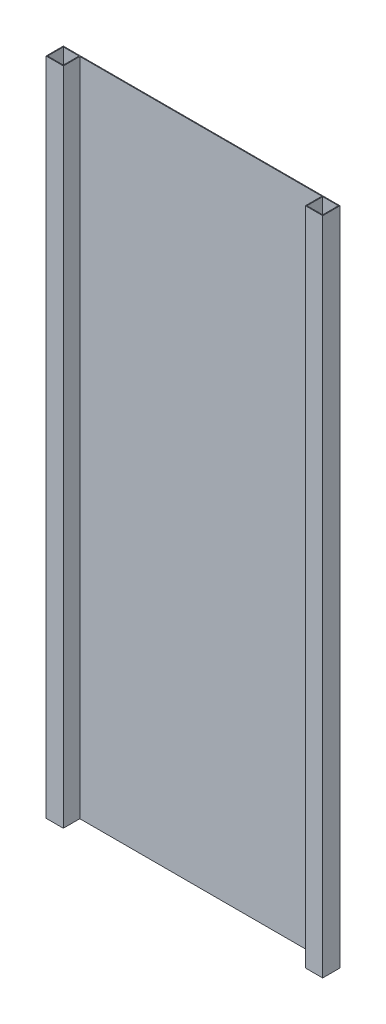
SolidWorks part; units mm, degrees
material "3.0205 (EN-AW 1200)"
ref_plane "정면" through (0, 0, 0) normal (0, 0, 1) x (1, 0, 0)
ref_plane "윗면" through (0, 0, 0) normal (0, 1, 0) x (1, 0, 0)
ref_plane "우측면" through (0, 0, 0) normal (1, 0, 0) x (0, 0, -1)
sketch "스케치2" plane through (0, 0, 0) normal (0, 0, 1) x (1, 0, 0)
  line L0 (-22, 840) -> (-22, 0)
  line L1 (0, 0) -> (-352, 0)
  line L2 (0, 0) -> (0, 840)
  line L3 (0, 840) -> (-352, 840)
  line L4 (-352, 0) -> (-352, 840)
  line L5 (-22, 0) -> (-22, 840)
  line L6 (-330, 840) -> (-330, 0)
  line L7 (-330, 0) -> (-330, 840)
  dimension "D1" = 840
  dimension "D2" = 352
  dimension "D3" = 22
  dimension "D4" = 22
extrude "보스-돌출1" add sketch "스케치2" along normal blind 1 contours L3 L6 L1 L0 region at (-176, 420, 0)
extrude "보스-돌출2" add sketch "스케치2<3>" along normal blind 22 contours L2 L3 L0 L1 | L6 L3 L4 L1 region at (-11, 420, 0) region at (-341, 420, 0)
sketch "스케치2<3>" plane through (0, 0, 0) normal (0, 0, 1) x (1, 0, 0) same geometry as "스케치2"
sketch "스케치4" plane through (0, 840, 0) normal (0, 1, 0) x (1, 0, 0)
  line L0 (0, 0) -> (0, -1)
  line L1 (0, -22) -> (0, 0) construction
  line L2 (0, -1) -> (-21, -1)
  line L3 (-21, -1) -> (-21, -21)
  line L4 (-21, -21) -> (-1, -21)
  line L5 (-1, -21) -> (-1, -1)
  line L6 (0, -22) -> (-22, -22) construction
  line L7 (-22, -22) -> (-22, -1) construction
  line L8 (-351, -21) -> (-351, -1)
  line L9 (-351, -1) -> (-331, -1)
  line L10 (-331, -1) -> (-331, -21)
  line L11 (-331, -21) -> (-351, -21)
  line L12 (0, 0) -> (-352, 0) construction
  line L13 (-330, -22) -> (-330, -1) construction
  line L14 (-330, -22) -> (-352, -22) construction
  line L15 (-352, -22) -> (-352, 0) construction
  dimension "D1" = 1
  dimension "D2" = 20
  dimension "D3" = 1
  dimension "D4" = 1
  dimension "D5" = 1
  dimension "D6" = 1
  dimension "D7" = 1
  dimension "D8" = 1
extrude "컷-돌출1" cut sketch "스케치4" against normal blind 840 contours L4 L5 L2 L3 region at (-11, 840, 11)
extrude "컷-돌출2" cut sketch "스케치4<3>" against normal blind 840 contours L11 L10 L9 L8 region at (-341, 840, 11)
sketch "스케치4<3>" plane through (0, 840, 0) normal (0, 1, 0) x (1, 0, 0) same geometry as "스케치4"
